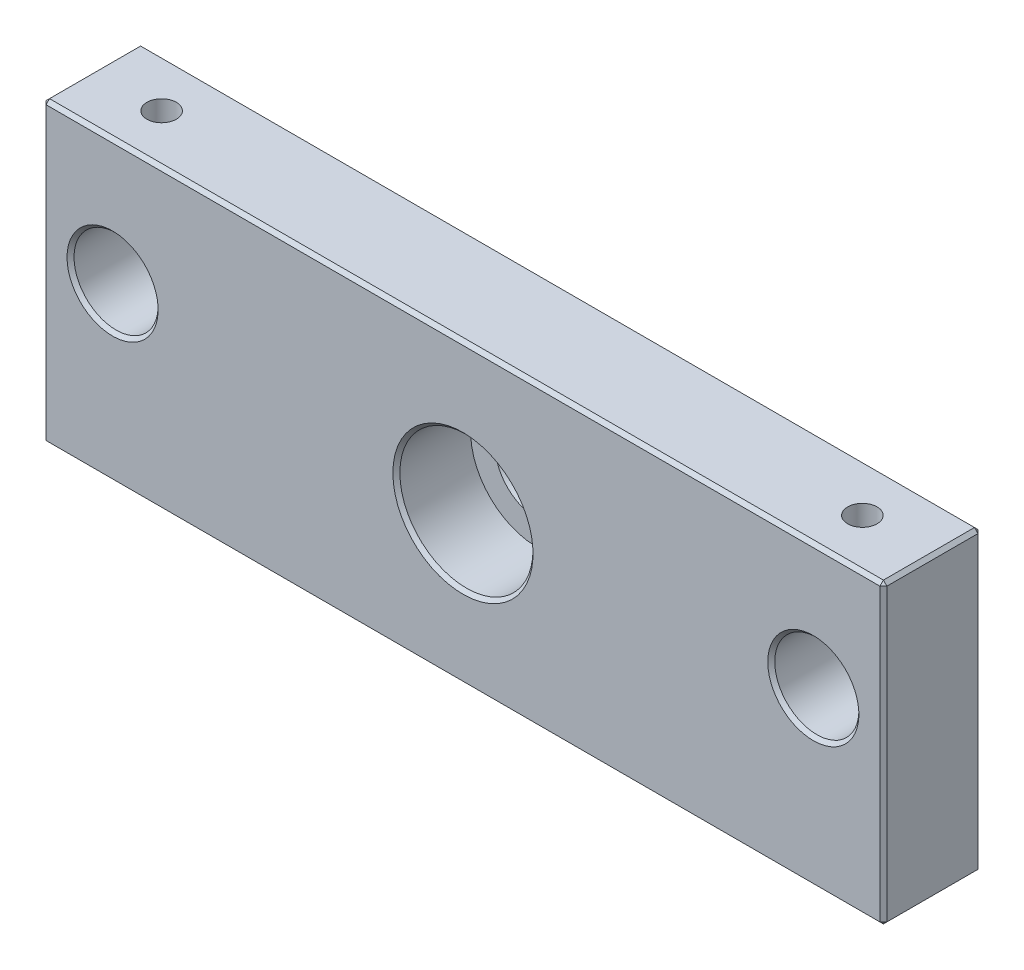
SolidWorks part; units mm, degrees
ref_plane "Front Plane" through (0, 0, 0) normal (0, 0, 1) x (1, 0, 0)
ref_plane "Top Plane" through (0, 0, 0) normal (0, 1, 0) x (1, 0, 0)
ref_plane "Right Plane" through (0, 0, 0) normal (1, 0, 0) x (0, 0, -1)
sketch "Sketch1" plane through (0, 0, 0) normal (0, 0, 1) x (1, 0, 0)
  line L1 (-60, -21.25) -> (60, -21.25)
  line L2 (-60, -21.25) -> (-60, 21.25)
  line L3 (-60, 21.25) -> (60, 21.25)
  line L4 (60, -21.25) -> (60, 21.25)
  line L5 (-60, -21.25) -> (60, 21.25) construction
  line L6 (-60, 21.25) -> (60, -21.25) construction
  point P0 (0, 0)
  dimension "D1" = 120
  dimension "D2" = 42.5
extrude "Boss-Extrude1" add sketch "Sketch1" along normal mid plane 14
sketch "Sketch2" plane through (0, 0, 7) normal (0, 0, 1) x (1, 0, 0)
  circle A0 centre (0, 0) radius 9.5
  dimension "D1" = 19
extrude "Cut-Extrude1" cut sketch "Sketch2" against normal blind 10.6
sketch "Sketch3" plane through (0, 0, -3.6) normal (0, 0, 1) x (1, 0, 0)
  circle A0 centre (0, 0) radius 5.5
  dimension "D1" = 11
extrude "Cut-Extrude2" cut sketch "Sketch3" against normal through all
sketch "Sketch5" plane through (0, 0, 7) normal (0, 0, 1) x (1, 0, 0)
  line L0 (-40.6477, 3.4) -> (36.4799, 3.4) construction
  circle A0 centre (-50, 3.4) radius 6
  circle A1 centre (50, 3.4) radius 6
  dimension "D1" = 12
  dimension "D2" = 12
  dimension "D4" = 50
  dimension "D3" = 50
  dimension "D5" = 3.4
extrude "Cut-Extrude4" cut sketch "Sketch5" against normal through all
hole_wizard "M5x0.8 Tapped Hole1" positions "Sketch9" profile "Sketch8" tap size "M5x0.8" standard "ANSI Metric"
sketch "Sketch9" plane through (0, -21.25, 0) normal (0, -1, 0) x (-1, 0, 0)
  line L0 (-1000, 0) -> (49000, 0) construction
  line L1 (60, -7) -> (60, 7) construction
  point P2 (25, 0)
  point P4 (37.5, 0)
  point P6 (50, 0)
  dimension "D1" = 10
  dimension "D2" = 22.5
  dimension "D3" = 35
sketch "Sketch8" plane through (-25, -21.25, 0) normal (1, 0, 0) x (0, 0, -1)
  line L0 (0, 0) -> (0, 12.0618)
  line L1 (0, 12.0618) -> (2.1, 10.8)
  line L2 (2.1, 10.8) -> (2.1, 0)
  line L5 (2.1, 0) -> (0, 0)
  line L10 (0, 12.0618) -> (-2.1, 10.8) construction
  line L11 (0, -6.35) -> (0, 107.95) construction
  dimension "Tap Drill Dia." = 4.2
  dimension "Tap Drill Depth" = 10.8
  dimension "Drill Angle" = 118
cosmetic thread "Hole Thread1" parameters "D1"=10, "D2"=5
cosmetic thread "Hole Thread2" parameters "D1"=10, "D2"=5
cosmetic thread "Hole Thread3" parameters "D1"=10, "D2"=5
mirror "Mirror1" about plane through (0, 0, 0) normal (1, 0, 0) of "M5x0.8 Tapped Hole1"
hole_wizard "M5x0.8 Tapped Hole2" positions "Sketch11" profile "Sketch10" tap size "M5x0.8" standard "ANSI Metric" end condition up to next
sketch "Sketch11" plane through (0, 21.25, 0) normal (0, 1, 0) x (1, 0, 0)
  line L0 (-1000, 0) -> (49000, 0) construction
  line L3 (-60, -7) -> (-60, 7) construction
  point P0 (-50, 0)
  point P2 (50, 0)
  point P17 (-60, 3.3758)
  point P22 (60, 1.8754)
  point P27 (60, 7)
  dimension "D1" = 10
  dimension "D2" = 10
sketch "Sketch10" plane through (-50, 21.25, 0) normal (1, 0, 0) x (0, 0, 1)
  line L0 (0, 0) -> (0, 11.85)
  line L1 (0, 11.85) -> (2.1, 11.85)
  line L2 (2.1, 11.85) -> (2.1, 0)
  line L5 (2.1, 0) -> (0, 0)
  line L11 (0, -6.35) -> (0, 107.95) construction
  dimension "Thru Tap Drill Dia." = 4.2
  dimension "Thru Tap Drill Depth" = 11.85
cosmetic thread "Hole Thread4" parameters "D2"=5
cosmetic thread "Hole Thread5" parameters "D2"=5
chamfer "Chamfer1" distance 0.5 angle 45 19 edges at (56, 3.4, -7) (-44, 3.4, -7) (5.5, 0, -7) (-44, 3.4, 7) (5.5, 0, -3.6) (9.5, 0, 7) (56, 3.4, 7) (-60, -21.25, 0) (-60, 0, -7) (60, 0, -7) (0, -21.25, -7) (60, -21.25, 0) (60, 0, 7) (0, -21.25, 7) (-60, 0, 7) (60, 21.25, 0) (0, 21.25, -7) (-60, 21.25, 0) (0, 21.25, 7)
